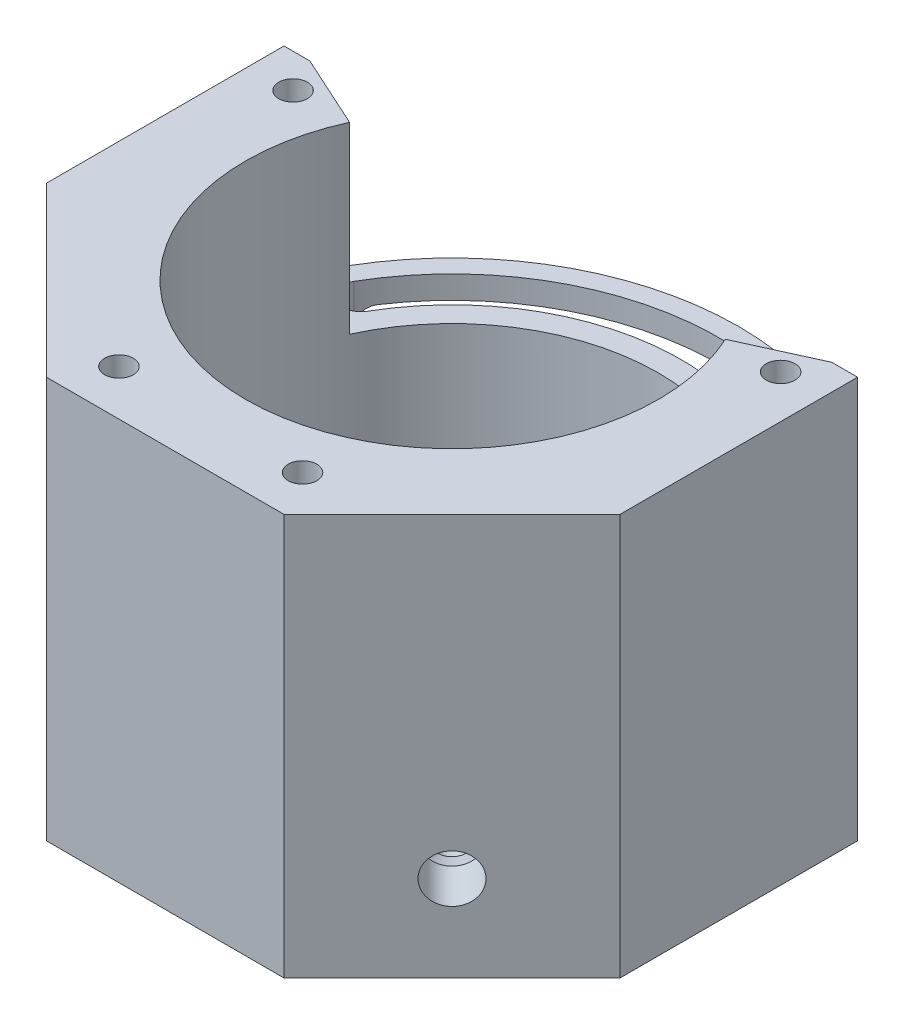
SolidWorks part; units mm, degrees
material "7075-T6 (SN)"
ref_plane "Front Plane" through (0, 0, 0) normal (0, 0, 1) x (1, 0, 0)
ref_plane "Top Plane" through (0, 0, 0) normal (0, 1, 0) x (1, 0, 0)
ref_plane "Right Plane" through (0, 0, 0) normal (1, 0, 0) x (0, 0, -1)
sketch "Sketch1" plane through (0, 0, 0) normal (0, 1, 0) x (1, 0, 0)
  line L1 (10.3553, 25) -> (-10.3553, 25)
  line L2 (-10.3553, 25) -> (-25, 10.3553)
  line L3 (-25, 10.3553) -> (-25, -10.3553)
  line L4 (-25, -10.3553) -> (-10.3553, -25)
  line L5 (-10.3553, -25) -> (10.3553, -25)
  line L6 (10.3553, -25) -> (25, -10.3553)
  line L7 (25, -10.3553) -> (25, 10.3553)
  line L8 (25, 10.3553) -> (10.3553, 25)
  circle A0 centre (0, 0) radius 25 construction
  dimension "D1" = 50
extrude "Boss-Extrude1" add sketch "Sketch1" along normal blind 35
sketch "Sketch2" plane through (0, 35, 0) normal (0, 1, 0) x (1, 0, 0)
  circle A0 centre (0, 0) radius 18
  dimension "D1" = 36
extrude "Cut-Extrude1" cut sketch "Sketch2" against normal up to next
sketch "Sketch3" plane through (0, 35, 0) normal (0, 1, 0) x (1, 0, 0)
  line L0 (-25, 10.3553) -> (-22.7545, 10.3553)
  line L1 (25, 10.3553) -> (22.7545, 10.3553)
  line L8 (25, 10.3553) -> (10.3553, 25)
  line L9 (10.3553, 25) -> (-10.3553, 25)
  line L10 (-10.3553, 25) -> (-25, 10.3553)
  line L11 (-25, 10.3553) -> (-25, -10.3553)
  line L12 (-25, -10.3553) -> (-10.3553, -25)
  line L13 (-10.3553, -25) -> (10.3553, -25)
  line L14 (10.3553, -25) -> (25, -10.3553)
  line L15 (25, -10.3553) -> (25, 10.3553)
  line L16 (25, 10.3553) -> (10.3553, 25)
  line L17 (10.3553, 25) -> (-10.3553, 25)
  line L18 (-10.3553, 25) -> (-25, 10.3553)
  line L19 (-25, 10.3553) -> (-25, -10.3553)
  line L20 (-25, -10.3553) -> (-10.3553, -25)
  line L21 (-10.3553, -25) -> (10.3553, -25)
  line L22 (10.3553, -25) -> (25, -10.3553)
  line L23 (25, -10.3553) -> (25, 10.3553)
  circle A0 centre (0, 0) radius 25
  line M11 (25, 10.3553) -> (10.3553, 25)
  line M12 (10.3553, 25) -> (-10.3553, 25)
  line M13 (-10.3553, 25) -> (-25, 10.3553)
  dimension "D1" = 0
extrude "Cut-Extrude2" cut sketch "Sketch3" against normal blind 22 contours A0 L17 M13 | A0 L18 L0 | A0 L16 M12 | A0 L1 M11 region at (-22.4071, 35, -12.2614) region at (-9.7323, 35, -23.4959) region at (9.7323, 35, -23.4959) region at (22.4071, 35, -12.2614)
sketch "Sketch4" plane through (0, 35, 0) normal (0, 1, 0) x (1, 0, 0)
  line L0 (25, 10.3553) -> (22.7545, 10.3553) construction
  line L1 (-16.3832, 7.4558) -> (-22.7545, 10.3553)
  line L2 (16.3832, 7.4558) -> (22.7545, 10.3553)
  line L3 (16.3832, 7.4558) -> (0, 0) construction
  line L4 (0, 0) -> (-16.3832, 7.4558) construction
  arc A1 (-22.7545, 10.3553) -> (22.7545, 10.3553) centre (0, 0) cw
  arc A2 (-16.3832, 7.4558) -> (16.3832, 7.4558) centre (0, 0) cw
  circle A5 centre (0, 0) radius 18 construction
extrude "Cut-Extrude3" cut sketch "Sketch4" against normal blind 16
ref_axis "Axis1" through (0, 0, 0) along (0, 1, 0)
sketch "Sketch5" plane through (0, 0, 0) normal (1, 0, 0) x (0, 0, -1)
  line L0 (25, 13) -> (25, 19) construction
  line L1 (25, 14) -> (20.5, 14)
  line L2 (25, 14) -> (25, 17)
  line L3 (25, 17) -> (20.5, 17)
  line L4 (20.5, 14) -> (20.5, 17)
  line L5 (25, 19) -> (10.3553, 19) construction
  dimension "D1" = 3
  dimension "D2" = 4.5
  dimension "D3" = 2
revolve "Cut-Revolve1" cut sketch "Sketch5" angle 120 mid plane about axis through (0, 0, 0) along (0, 1, 0)
fillet "Fillet2" radius 1.5 4 edges at (19.7021, 14, -11.375) (19.7021, 17, -11.375) (-19.7021, 17, -11.375) (-19.7021, 14, -11.375)
sketch "Sketch9" plane through (0, 19, 0) normal (0, 1, 0) x (1, 0, 0)
  arc A0 (-18.7494, 10.825) -> (18.7494, 10.825) centre (0, 0) cw construction
  arc A1 (20.1784, 11.65) -> (-20.1784, 11.65) centre (0, 0) ccw
  arc A2 (17.3205, 10) -> (-17.3205, 10) centre (0, 0) ccw
  arc A3 (17.3205, 10) -> (20.1784, 11.65) centre (18.7494, 10.825) ccw
  arc A4 (-20.1784, 11.65) -> (-17.3205, 10) centre (-18.7494, 10.825) ccw
  arc A5 (16.3832, 7.4558) -> (-16.3832, 7.4558) centre (0, 0) ccw construction
  point P4 (0, 21.65)
  point P18 (0, 20)
  dimension "D1" = 3.3
  dimension "D2" = 2
  dimension "D3" = 120
extrude "Cut-Extrude7" cut sketch "Sketch9" against normal blind 6.5
hole_wizard "M3x0.25 Tapped Hole1" positions "Sketch10" profile "Sketch11" tap size "M3x0.25" standard "DIN" end condition up to next
sketch "Sketch10" plane through (-17.6777, 0, -17.6777) normal (-0.7071, 0, -0.7071) x (-0.7071, 0, 0.7071)
  line L0 (-10.3553, 0) -> (10.3553, 0) construction
  point P0 (0, 7.5)
  dimension "D1" = 7.5
sketch "Sketch11" plane through (-17.6777, 7.5, -17.6777) normal (0, 1, 0) x (-0.7071, 0, 0.7071)
  line L0 (0, 0) -> (0, 7)
  line L1 (0, 7) -> (1.375, 7)
  line L2 (1.375, 7) -> (1.375, 0)
  line L5 (1.375, 0) -> (0, 0)
  line L11 (0, -6.35) -> (0, 107.95) construction
  dimension "Thru Tap Drill Dia." = 2.75
  dimension "Thru Tap Drill Depth" = 7
cosmetic thread "Hole Thread1" parameters "D2"=3
hole_wizard "M3x0.25 Tapped Hole2" positions "Sketch12" profile "Sketch13" tap size "M3x0.25" standard "DIN" end condition up to next
sketch "Sketch12" plane through (17.6777, 0, -17.6777) normal (0.7071, 0, -0.7071) x (-0.7071, 0, -0.7071)
  line L0 (-10.3553, 0) -> (10.3553, 0) construction
  point P0 (0, 7.5)
  dimension "D1" = 7.5
sketch "Sketch13" plane through (17.6777, 7.5, -17.6777) normal (0, 1, 0) x (-0.7071, 0, -0.7071)
  line L0 (0, 0) -> (0, 7)
  line L1 (0, 7) -> (1.375, 7)
  line L2 (1.375, 7) -> (1.375, 0)
  line L5 (1.375, 0) -> (0, 0)
  line L11 (0, -6.35) -> (0, 107.95) construction
  dimension "Thru Tap Drill Dia." = 2.75
  dimension "Thru Tap Drill Depth" = 7
cosmetic thread "Hole Thread2" parameters "D2"=3
sketch "Sketch15" plane through (17.6777, 0, 17.6777) normal (0.7071, 0, 0.7071) x (0.7071, 0, -0.7071)
  circle A0 centre (0, 7.5) radius 1.6
  circle A1 centre (0, 7.5) radius 1.375 construction
  dimension "D1" = 3.2
extrude "Cut-Extrude8" cut sketch "Sketch15" against normal up to next
sketch "Sketch16" plane through (-17.6777, 0, 17.6777) normal (-0.7071, 0, 0.7071) x (0.7071, 0, 0.7071)
  circle A0 centre (0, 7.5) radius 1.6
  circle A1 centre (0, 7.5) radius 1.375 construction
  dimension "D1" = 3.2
extrude "Cut-Extrude9" cut sketch "Sketch16" against normal up to next
hole_wizard "M5 Tapped Hole3" positions "Sketch26" profile "Sketch27" tap size "M5" standard "DIN"
sketch "Sketch26" plane through (-17.6777, 0, 17.6777) normal (-0.7071, 0, 0.7071) x (0.7071, 0, 0.7071)
  circle A0 centre (0, 7.5) radius 1.6 construction
  point P0 (0, 7.5)
sketch "Sketch27" plane through (-17.6777, 7.5, 17.6777) normal (0, 1, 0) x (0.7071, 0, 0.7071)
  line L0 (0, 0) -> (0, 5.5618)
  line L1 (0, 5.5618) -> (2.1, 4.3)
  line L2 (2.1, 4.3) -> (2.1, 0)
  line L5 (2.1, 0) -> (0, 0)
  line L10 (0, 5.5618) -> (-2.1, 4.3) construction
  line L11 (0, -6.35) -> (0, 107.95) construction
  dimension "Tap Drill Dia." = 4.2
  dimension "Tap Drill Depth" = 4.3
  dimension "Drill Angle" = 118
cosmetic thread "Hole Thread5" parameters "D1"=3, "D2"=5
hole_wizard "M5 Tapped Hole4" positions "Sketch28" profile "Sketch29" tap size "M5" standard "DIN"
sketch "Sketch28" plane through (17.6777, 0, 17.6777) normal (0.7071, 0, 0.7071) x (0.7071, 0, -0.7071)
  point P0 (0, 7.5)
sketch "Sketch29" plane through (17.6777, 7.5, 17.6777) normal (0, 1, 0) x (0.7071, 0, -0.7071)
  line L0 (0, 0) -> (0, 5.5618)
  line L1 (0, 5.5618) -> (2.1, 4.3)
  line L2 (2.1, 4.3) -> (2.1, 0)
  line L5 (2.1, 0) -> (0, 0)
  line L10 (0, 5.5618) -> (-2.1, 4.3) construction
  line L11 (0, -6.35) -> (0, 107.95) construction
  dimension "Tap Drill Dia." = 4.2
  dimension "Tap Drill Depth" = 4.3
  dimension "Drill Angle" = 118
cosmetic thread "Hole Thread6" parameters "D1"=3, "D2"=5
hole_wizard "M3 Tapped Hole1" positions "Sketch30" profile "Sketch31" tap size "M3" standard "DIN"
sketch "Sketch30" plane through (0, 35, 0) normal (0, 1, 0) x (1, 0, 0)
  line L0 (-21.25, 7.3951) -> (0, 0) construction
  line L1 (0, 0) -> (21.25, 7.3951) construction
  line L3 (8, -21.0297) -> (0, 0) construction
  line L5 (-8, -21.0297) -> (0, 0) construction
  point P0 (-21.25, 7.3951)
  point P2 (21.25, 7.3951)
  point P4 (-8, -21.0297)
  point P6 (8, -21.0297)
  dimension "D1" = 22.5
  dimension "D2" = 16
  dimension "D3" = 42.5
sketch "Sketch31" plane through (-21.25, 35, -7.3951) normal (1, 0, 0) x (0, 0, 1)
  line L0 (0, 0) -> (0, 12.2511)
  line L1 (0, 12.2511) -> (1.25, 11.5)
  line L2 (1.25, 11.5) -> (1.25, 0)
  line L5 (1.25, 0) -> (0, 0)
  line L10 (0, 12.2511) -> (-1.25, 11.5) construction
  line L11 (0, -6.35) -> (0, 107.95) construction
  dimension "Tap Drill Dia." = 2.5
  dimension "Tap Drill Depth" = 11.5
  dimension "Drill Angle" = 118
cosmetic thread "Hole Thread7" parameters "D1"=10, "D2"=3
cosmetic thread "Hole Thread8" parameters "D1"=10, "D2"=3
cosmetic thread "Hole Thread9" parameters "D1"=10, "D2"=3
cosmetic thread "Hole Thread10" parameters "D1"=10, "D2"=3
fillet "Fillet3" radius 1.5 2 edges at (22.7545, 16, -10.3553) (-22.7545, 16, -10.3553)
